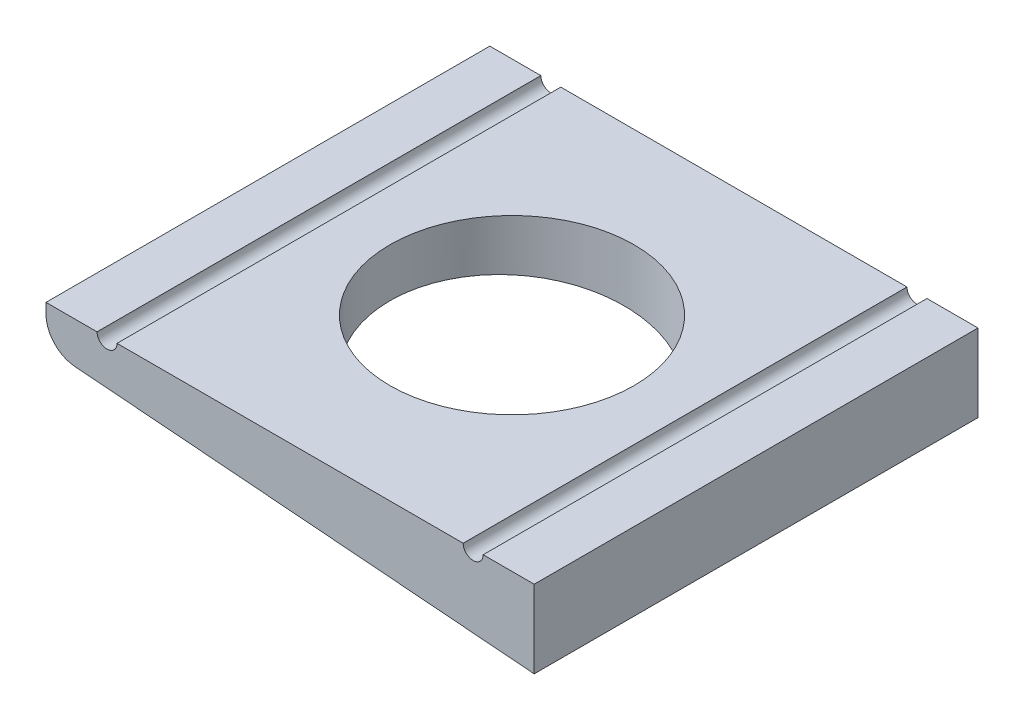
SolidWorks part; units mm, degrees
extrude "Base-Extrude" add sketch "Sketch1" along normal mid plane 40
sketch "Sketch1" plane through (0, 0, 0) normal (0, 0, 1) x (1, 0, 0)
  line L0 (22, 0) -> (-22, 0)
  line L1 (22, 0) -> (22, -7)
  line L2 (-22, 0) -> (-22, -0.9139)
  line L3 (22, -7) -> (-19.422, -3.7051)
  line L4 (0, 0) -> (0, -5.25) construction
  arc A0 (-19.422, -3.7051) -> (-22, -0.9139) centre (-19.2, -0.9139) cw
  dimension "D2" = 22
ref_plane "Plane1" through (0, 0, 0) normal (0, 0, 1) x (1, 0, 0)
ref_plane "Plane2" through (0, 0, 0) normal (0, 1, 0) x (1, 0, 0)
ref_plane "Plane3" through (0, 0, 0) normal (1, 0, 0) x (0, 0, -1)
sketch "Sketch2" plane through (0, 0, 0) normal (0, 1, 0) x (-1, 0, 0)
  circle A0 centre (0, 0) radius 11
extrude "Cut-Extrude1" cut sketch "Sketch2" against normal through all
sketch "Sketch3" plane through (0, 0, 20) normal (0, 0, 1) x (1, 0, 0)
  line L0 (22, 0) -> (-22, 0) construction
  circle A0 centre (16.5, 0) radius 0.9
  circle A1 centre (-16.5, 0) radius 0.9
  dimension "T" = 0.9
  dimension "D1" = 0.9
  dimension "D2" = 16.5
  dimension "D3" = 16.5
extrude "ID-Grooves" cut sketch "Sketch3" against normal through all
equation "\"D2@Sketch1\" = \"B@Sketch1\" / 2"
equation "\"D2@Sketch3\" =  ( \"D@Sketch2\" / 2 )  +  ( \"B@Sketch1\" -  \"D@Sketch2\" )  / 4"
equation "\"D3@Sketch3\" = \"D2@Sketch3\""
equation "\"D1@Sketch3\" = \"T@Sketch3\""
